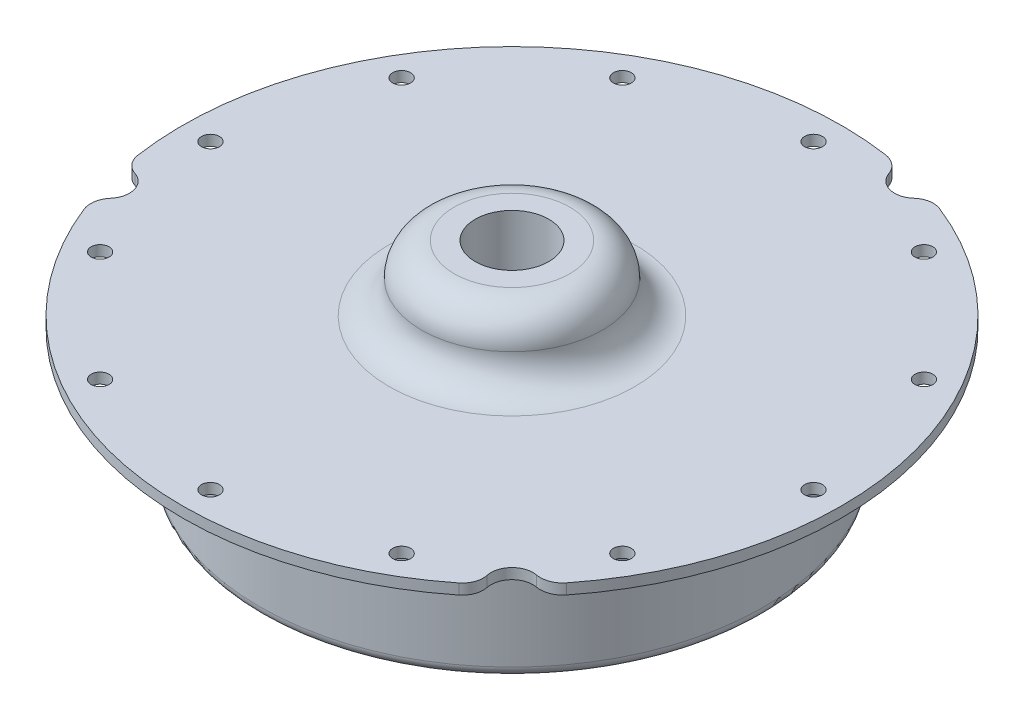
SolidWorks part; units mm, degrees
material "6063-T6"
ref_plane "Front Plane" through (0, 0, 0) normal (0, 0, 1) x (1, 0, 0)
ref_plane "Top Plane" through (0, 0, 0) normal (0, 1, 0) x (1, 0, 0)
ref_plane "Right Plane" through (0, 0, 0) normal (1, 0, 0) x (0, 0, -1)
ref_axis "Axis1" through (0, 55, 0) along (0, -1, 0)
sketch "Sketch1" plane through (0, 0, 0) normal (0, 0, 1) x (1, 0, 0)
  line L0 (-49.784, 0) -> (-39.6875, 0)
  line L1 (0, 55) -> (0, -55) construction
  line L2 (-49.784, 0) -> (-49.784, 1.5875)
  line L3 (-5.5562, 11.43) -> (-8.7312, 11.43)
  line L5 (-5.5562, 11.43) -> (-5.5562, 0)
  line L6 (-5.5562, 0) -> (0, 0) construction
  line L7 (-49.784, 0) -> (-49.784, 1.5875) construction
  line L8 (-5.5562, 1.5875) -> (-5.5562, 0) construction
  line L9 (-38.1, -1.5875) -> (-38.1, -17.4625)
  line L11 (-34.925, -17.4625) -> (-34.925, -3.175)
  line L12 (-31.75, 0) -> (-5.5562, 0)
  line L13 (0, -201000) -> (0, 249000) construction
  line L14 (-49.784, 1.5875) -> (-18.5737, 1.5875)
  arc A0 (-34.925, -3.175) -> (-31.75, 0) centre (-31.75, -3.175) cw
  arc A1 (-38.1, -1.5875) -> (-39.6875, 0) centre (-39.6875, -1.5875) ccw
  arc A2 (-18.5737, 1.5875) -> (-13.6525, 6.5088) centre (-18.5737, 6.5088) ccw
  arc A3 (-8.7312, 11.43) -> (-13.6525, 6.5088) centre (-8.7312, 6.5088) ccw
  arc A4 (-38.1, -17.4625) -> (-34.925, -17.4625) centre (-36.5125, -17.4625) ccw
  point P18 (-34.925, 0)
  dimension "D4" = 3.175
  dimension "D5" = 1.5875
  dimension "D1" = 3.175
  dimension "D2" = 38.1
  dimension "D3" = 17.4625
  dimension "D6" = 1.5875
  dimension "D7" = 3.175
  dimension "D8" = 11.43
revolve "Revolve1" add sketch "Sketch1" angle 360 about axis through (0, 55, 0) along (0, -1, 0)
ref_plane "Hole Location Plane" through (0, 3.175, 0) normal (0, 1, 0) x (1, 0, 0)
sketch "Hole Location" plane through (0, 3.175, 0) normal (0, 1, 0) x (1, 0, 0)
  line L0 (0, 0) -> (-45.5549, 0) construction
  circle A0 centre (0, 0) radius 45.5549 construction
  point P3 (0, 0)
  dimension "D1" = 91.1098
hole_wizard "#36 (0.1065) Diameter Hole1" positions "Sketch2" profile "Sketch3" hole size "#36" standard "ANSI Inch" end condition through all
sketch "Sketch2" plane through (0, 1.5875, 0) normal (0, 1, 0) x (1, 0, 0)
  point P0 (-45.5549, 0)
sketch "Sketch3" plane through (-45.5549, 1.5875, 0) normal (1, 0, 0) x (0, 0, 1)
  line L0 (0, 0) -> (0, 20.6375)
  line L1 (0, 20.6375) -> (1.3525, 20.6375)
  line L2 (1.3525, 20.6375) -> (1.3525, 0)
  line L5 (1.3525, 0) -> (0, 0)
  line L11 (0, -6.35) -> (0, 107.95) construction
  dimension "Thru Hole Dia." = 2.7051
  dimension "Thru Hole Depth" = 20.6375
pattern_circular "CirPattern1" count 12 over 360 of "#36 (0.1065) Diameter Hole1"
hole_wizard "7/16 (0.4375) Diameter Hole1" positions "Sketch4" profile "Sketch5" hole size "7/16" standard "ANSI Inch" end condition through all
sketch "Sketch4" plane through (0, 11.43, 0) normal (0, 1, 0) x (1, 0, 0)
  point P0 (0, 0)
sketch "Sketch5" plane through (0, 11.43, 0) normal (1, 0, 0) x (0, 0, 1)
  line L0 (0, 0) -> (0, 30.48)
  line L1 (0, 30.48) -> (5.5562, 30.48)
  line L2 (5.5562, 30.48) -> (5.5562, 0)
  line L5 (5.5562, 0) -> (0, 0)
  line L11 (0, -6.35) -> (0, 107.95) construction
  dimension "Thru Hole Dia." = 11.1125
  dimension "Thru Hole Depth" = 30.48
sketch "Sketch6" plane through (0, 1.5875, 0) normal (0, 1, 0) x (1, 0, 0)
  line L0 (0, 0) -> (-48.0877, -12.885) construction
  line L1 (0, 0) -> (-45.5549, 0) construction
  circle A0 centre (0, 0) radius 49.784 construction
  arc A1 (-49.2429, -7.3202) -> (-47.095, -9.8692) centre (-46.1024, -6.8534) ccw
  arc A2 (-47.095, -9.8692) -> (-45.6723, -14.9458) centre (-48.0877, -12.885) cw
  circle A3 centre (0, 0) radius 49.784 construction
  arc A4 (-45.6723, -14.9458) -> (-46.2472, -18.4294) centre (-43.0722, -17.1641) ccw
  arc A5 (-46.2472, -18.4294) -> (-49.2429, -7.3202) centre (0, 0) cw
  arc A6 (9.8927, 47.0263) -> (7.1633, 49.2659) centre (6.6715, 45.8837) ccw
  arc A7 (15.0005, 45.7201) -> (9.8927, 47.0263) centre (12.885, 48.0877) cw
  arc A8 (18.282, 46.3057) -> (15.0005, 45.7201) centre (17.116, 43.3525) ccw
  arc A9 (7.1633, 49.2659) -> (18.282, 46.3057) centre (0, 0) cw
  arc A10 (35.7796, -32.0805) -> (39.0839, -30.8366) centre (36.4007, -28.7196) ccw
  arc A11 (32.0945, -35.8509) -> (35.7796, -32.0805) centre (35.2026, -35.2026) cw
  arc A12 (30.9609, -38.9855) -> (32.0945, -35.8509) centre (28.9864, -36.4992) ccw
  arc A13 (39.0839, -30.8366) -> (30.9609, -38.9855) centre (0, 0) cw
  point P31 (0, 0)
  circle M16 centre (0, 0) radius 49.784
  dimension "D2" = 3.175
  dimension "D3" = 3.175
  dimension "D4" = 49.784
  dimension "D5" = 3.175
  dimension "D1" = 15
  dimension "D6" = 3
extrude "Cut-Extrude1" cut sketch "Sketch6" against normal up to surface (1.5875 mm away) contours L0 | A4 A2 A1 M16 | A12 A10 A11 M16 | A7 A6 A9 A8 region at (-46.8529, 1.5875, 12.5779) region at (34.3192, 1.5875, 34.2869) up to face at (-39.4517, 0, -24.13)
equation "\"D1@Hole Location\"=\"TANK DIAMETER@Cryo Tank.Assembly\"+\"GASKET SEAT THICKNESS@Cryo Tank.Assembly\"+\"LINER THICKNESS@Cryo Tank.Assembly\"+\"SHRINK FIT DELTA@Cryo Tank.Assembly\""
equation "\"D2@Sketch1\"=\"TANK DIAMETER@Cryo Tank.Assembly\"/2"
equation "\"D3@Sketch1\"=0.5+0.125+0.0625"
